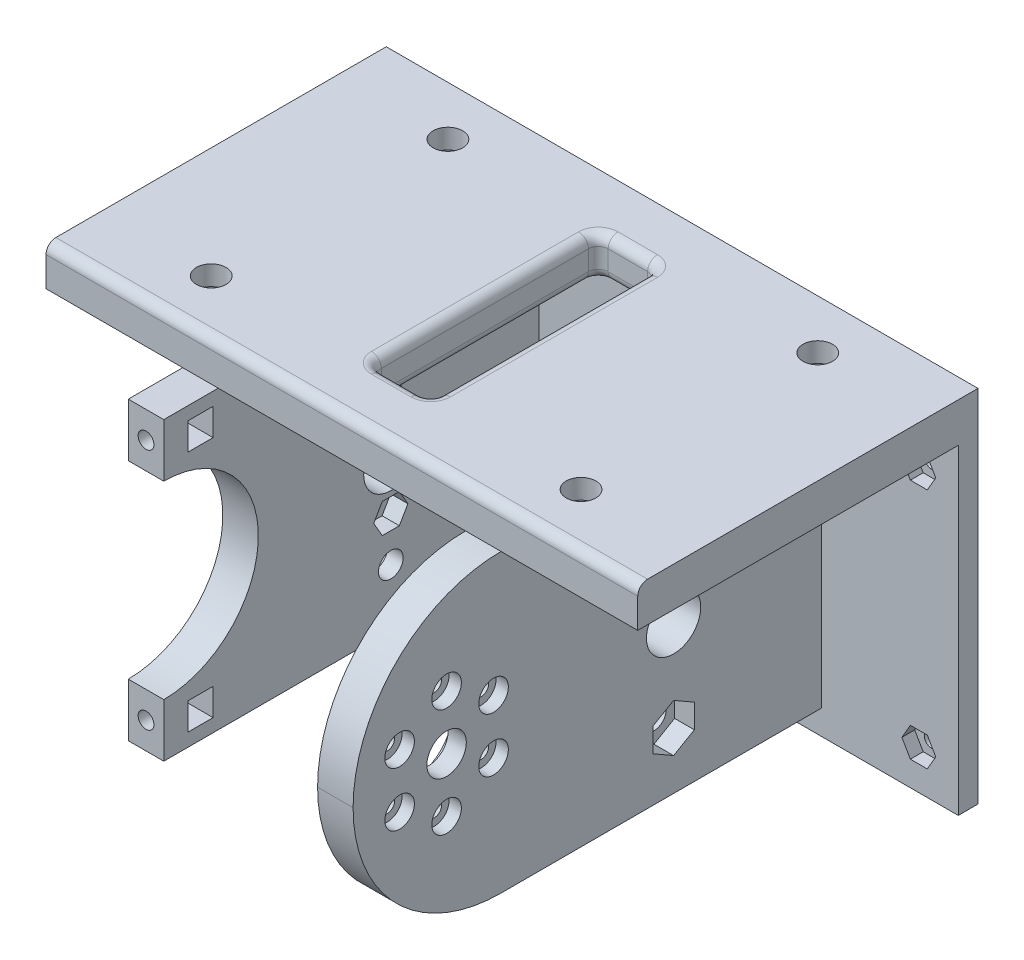
SolidWorks part; units mm, degrees
ref_plane "Front Plane" through (0, 0, 0) normal (0, 0, 1) x (1, 0, 0)
ref_plane "Top Plane" through (0, 0, 0) normal (0, 1, 0) x (1, 0, 0)
ref_plane "Right Plane" through (0, 0, 0) normal (1, 0, 0) x (0, 0, -1)
sketch "Sketch1" plane through (0, 0, 0) normal (0, 1, 0) x (1, 0, 0)
  line L0 (0, 18.2197) -> (0, -18.3609) construction
  line L1 (-19.3496, 0) -> (20.197, 0) construction
  line L2 (-37.5, 0) -> (-37.5, -10) construction
  line L3 (60, 35) -> (-60, 35)
  line L4 (-60, 35) -> (-60, -35)
  line L5 (60, -35) -> (-60, -35)
  line L6 (60, 35) -> (60, -35)
  line L7 (6, 23) -> (-6, 23)
  line L8 (-6, 23) -> (-6, -23)
  line L9 (6, -23) -> (-6, -23)
  line L10 (6, 23) -> (6, -23)
  circle A0 centre (-37.5, 0) radius 10 construction
  circle A6 centre (-37.5, 24) radius 3
  circle A7 centre (-37.5, 24) radius 3.4 construction
  circle A8 centre (-37.5, -24) radius 3
  circle A9 centre (-37.5, -24) radius 3.4 construction
  circle A10 centre (37.5, 24) radius 3
  circle A11 centre (37.5, 24) radius 3.4 construction
  circle A12 centre (37.5, 0) radius 10 construction
  circle A13 centre (37.5, -24) radius 3.4 construction
  circle A14 centre (37.5, -24) radius 3
  point P18 (-60, 0)
  point P20 (0, 35)
  point P21 (0, -35)
  point P33 (-6, 0)
  point P35 (0, -23)
  point P36 (0, 23)
  dimension "D1" = 20
  dimension "D3" = 6.8
  dimension "D4" = 48
  dimension "D5" = 75
  dimension "D2" = 6
  dimension "D6" = 120
  dimension "D7" = 70
  dimension "D8" = 12
  dimension "D9" = 46
extrude "Boss-Extrude1" add sketch "Sketch1" along normal blind 8
fillet "Fillet1" radius 2 4 edges at (6, 4, 23) (-6, 4, 23) (6, 4, -23) (-6, 4, -23)
sketch "Sketch2" plane through (0, 0, 0) normal (0, -1, 0) x (1, 0, 0)
  line L0 (-60, -35) -> (-60, -30)
  line L1 (-60, -35) -> (-60, 35) construction
  line L2 (-60, -30) -> (60, -30)
  line L3 (60, 35) -> (60, -35) construction
  line L4 (60, -30) -> (60, -35)
  line L5 (60, -35) -> (-60, -35)
  dimension "D1" = 5
extrude "Boss-Extrude2" add sketch "Sketch2" along normal blind 65
sketch "Sketch3" plane through (0, 0, -30) normal (0, 0, 1) x (1, 0, 0)
  line L0 (0, 0) -> (0, -65) construction
  line L1 (60, 0) -> (-60, 0) construction
  line L2 (60, -65) -> (-60, -65) construction
  line L3 (0, -32.5) -> (-60, -32.5) construction
  line L4 (-60, -65) -> (-60, 0) construction
  line L5 (0, -32.5) -> (60, -32.5) construction
  line L6 (60, -65) -> (60, 0) construction
  line L8 (30, 0) -> (30, -65) construction
  line L9 (-25.075, 0) -> (-32.275, 0)
  line L10 (-32.275, 0) -> (-32.275, -60)
  line L11 (-32.275, -60) -> (-25.075, -60)
  line L12 (-25.075, 0) -> (-25.075, -60)
  line L13 (25.075, 0) -> (25.075, -60)
  line L14 (32.275, -60) -> (25.075, -60)
  line L15 (32.275, 0) -> (32.275, -60)
  line L16 (25.075, 0) -> (32.275, 0)
  point P18 (30, -32.5)
  dimension "D1" = 7.2
  dimension "D2" = 50.15
  dimension "D3" = 60
extrude "Boss-Extrude3" add sketch "Sketch3" along normal blind 45
sketch "Sketch4" plane through (-32.275, 0, 0) normal (-1, 0, 0) x (0, 0, 1)
  line L0 (0, 0) -> (0, -60) construction
  line L1 (15, -60) -> (-30, -60) construction
  line L2 (-30, -30) -> (15, -30) construction
  line L3 (-30, 0) -> (-30, -60) construction
  line L4 (15, 0) -> (15, -60) construction
  circle A0 centre (0, -30) radius 5.5
  circle A1 centre (0, -30) radius 18.5 construction
  circle A2 centre (0, -11.5) radius 2.5
  circle A3 centre (0, -48.5) radius 2.5
  dimension "D1" = 11
  dimension "D2" = 37
  dimension "5" = 5
extrude "Cut-Extrude1" cut sketch "Sketch4" against normal through all both and the other way through all
sketch "Sketch5" plane through (-32.275, 0, 0) normal (-1, 0, 0) x (0, 0, 1)
  line L0 (-30, 0) -> (-30, -60) construction
  line L1 (4.2, -9.0751) -> (0, -6.6503)
  line L2 (0, -6.6503) -> (-4.2, -9.0751)
  line L3 (-4.2, -9.0751) -> (-4.2, -13.9249)
  line L4 (-4.2, -13.9249) -> (0, -16.3497)
  line L5 (0, -16.3497) -> (4.2, -13.9249)
  line L6 (4.2, -13.9249) -> (4.2, -9.0751)
  line L7 (4.2, -46.0751) -> (0, -43.6503)
  line L8 (0, -43.6503) -> (-4.2, -46.0751)
  line L9 (-4.2, -46.0751) -> (-4.2, -50.9249)
  line L10 (-4.2, -50.9249) -> (0, -53.3497)
  line L11 (0, -53.3497) -> (4.2, -50.9249)
  line L12 (4.2, -50.9249) -> (4.2, -46.0751)
  line L13 (-30, -65) -> (-30, 0) construction
  circle A0 centre (0, -11.5) radius 4.2 construction
  circle A1 centre (0, -48.5) radius 4.2 construction
  point P10 (2.1, -52.1373)
  dimension "D1" = 8.4
  dimension "D2" = 8.4
extrude "Cut-Extrude2" cut sketch "Sketch5" against normal blind 4
sketch "Sketch6" plane through (32.275, 0, 0) normal (1, 0, 0) x (0, 0, -1)
  line L0 (30, -65) -> (30, 0) construction
  line L1 (4.2, -13.9249) -> (4.2, -9.0751)
  line L2 (4.2, -9.0751) -> (0, -6.6503)
  line L3 (0, -6.6503) -> (-4.2, -9.0751)
  line L4 (-4.2, -9.0751) -> (-4.2, -13.9249)
  line L5 (-4.2, -13.9249) -> (0, -16.3497)
  line L6 (0, -16.3497) -> (4.2, -13.9249)
  line L7 (-4.2, -46.0751) -> (-4.2, -50.9249)
  line L8 (-4.2, -50.9249) -> (0, -53.3497)
  line L9 (0, -53.3497) -> (4.2, -50.9249)
  line L10 (4.2, -50.9249) -> (4.2, -46.0751)
  line L11 (4.2, -46.0751) -> (0, -43.6503)
  line L12 (0, -43.6503) -> (-4.2, -46.0751)
  circle A0 centre (0, -11.5) radius 4.2 construction
  circle A1 centre (0, -48.5) radius 4.2 construction
  dimension "D1" = 8.4
  dimension "D2" = 8.4
extrude "Cut-Extrude3" cut sketch "Sketch6" against normal blind 4
sketch "Sketch7" plane through (0, 0, 0) normal (0, -1, 0) x (1, 0, 0)
  line L0 (32.275, 15) -> (32.275, -30) construction
  line L1 (42.7, -20.9978) -> (37.5, -17.9956)
  line L2 (37.5, -17.9956) -> (32.3, -20.9978)
  line L3 (32.3, -20.9978) -> (32.3, -27.0022)
  line L4 (32.3, -27.0022) -> (37.5, -30.0044)
  line L5 (37.5, -30.0044) -> (42.7, -27.0022)
  line L6 (42.7, -27.0022) -> (42.7, -20.9978)
  line L7 (42.7, 27.0022) -> (37.5, 30.0044)
  line L8 (37.5, 30.0044) -> (32.3, 27.0022)
  line L9 (32.3, 27.0022) -> (32.3, 20.9978)
  line L10 (32.3, 20.9978) -> (37.5, 17.9956)
  line L11 (37.5, 17.9956) -> (42.7, 20.9978)
  line L12 (42.7, 20.9978) -> (42.7, 27.0022)
  line L13 (0, 0) -> (0, 40) construction
  line L14 (-42.7, -27.0022) -> (-42.7, -20.9978)
  line L15 (-37.5, -30.0044) -> (-42.7, -27.0022)
  line L16 (-32.3, -27.0022) -> (-37.5, -30.0044)
  line L17 (-32.3, -20.9978) -> (-32.3, -27.0022)
  line L18 (-37.5, -17.9956) -> (-32.3, -20.9978)
  line L19 (-42.7, -20.9978) -> (-37.5, -17.9956)
  line L20 (-42.7, 20.9978) -> (-42.7, 27.0022)
  line L21 (-37.5, 17.9956) -> (-42.7, 20.9978)
  line L22 (-32.3, 20.9978) -> (-37.5, 17.9956)
  line L23 (-32.3, 27.0022) -> (-32.3, 20.9978)
  line L24 (-37.5, 30.0044) -> (-32.3, 27.0022)
  line L25 (-42.7, 27.0022) -> (-37.5, 30.0044)
  circle A0 centre (37.5, -24) radius 5.2 construction
  circle A1 centre (37.5, 24) radius 5.2 construction
  circle A3 centre (-37.5, -24) radius 5.2 construction
  circle A4 centre (-37.5, 24) radius 5.2 construction
  dimension "D1" = 10.4
  dimension "D2" = 10.4
extrude "Cut-Extrude4" cut sketch "Sketch7" against normal blind 4
fillet "Fillet3" radius 2 17 edges at (5.4142, 0, 22.4142) (0, 0, 23) (-5.4142, 0, 22.4142) (-6, 0, 0) (-5.4142, 0, -22.4142) (0, 0, -23) (5.4142, 0, -22.4142) (5.4142, 8, 22.4142) (0, 8, 23) (-5.4142, 8, 22.4142) (-6, 8, 0) (-5.4142, 8, -22.4142) (0, 8, -23) (5.4142, 8, -22.4142) (6, 0, 0) (6, 8, 0) (0, 8, 35)
sketch "Sketch10" plane through (0, 0, 15) normal (0, 0, 1) x (1, 0, 0)
  line L8 (-25.075, -60) -> (-25.075, 0)
  line L9 (-25.075, 0) -> (-32.275, 0)
  line L10 (-32.275, 0) -> (-32.275, -60)
  line L11 (-32.275, -60) -> (-25.075, -60)
  line L12 (-25.075, -60) -> (-25.075, 0)
  line L13 (-25.075, 0) -> (-32.275, 0)
  line L14 (-32.275, 0) -> (-32.275, -60)
  line L15 (-32.275, -60) -> (-25.075, -60)
  line L16 (32.275, 0) -> (25.075, 0)
  line L17 (25.075, 0) -> (25.075, -60)
  line L18 (25.075, -60) -> (32.275, -60)
  line L19 (32.275, -60) -> (32.275, 0)
  line L20 (32.275, 0) -> (25.075, 0)
  line L21 (25.075, 0) -> (25.075, -60)
  line L22 (25.075, -60) -> (32.275, -60)
  line L23 (32.275, -60) -> (32.275, 0)
  dimension "D1" = 0
  dimension "D2" = 0
extrude "Boss-Extrude4" add sketch "Sketch10" along normal blind 50
sketch "Sketch11" plane through (32.275, 0, 0) normal (1, 0, 0) x (0, 0, -1)
  line L0 (0, -30) -> (-46.04, -30) construction
  circle A0 centre (-46.04, -30) radius 4
  dimension "D2" = 8
  dimension "D1" = 46.04
extrude "Cut-Extrude7" cut sketch "Sketch11" against normal through all
sketch "Sketch13" plane through (32.275, 0, 0) normal (1, 0, 0) x (0, 0, -1)
  circle A0 centre (-46.04, -30) radius 11 construction
  circle A1 centre (-46.04, -19) radius 1.5
  circle A2 centre (-55.5663, -24.5) radius 1.5
  circle A3 centre (-55.5663, -35.5) radius 1.5
  circle A4 centre (-46.04, -41) radius 1.5
  circle A5 centre (-36.5137, -35.5) radius 1.5
  circle A6 centre (-36.5137, -24.5) radius 1.5
  point P17 (-46.04, -30)
  dimension "D1" = 22
  dimension "D2" = 3
  dimension "D3" = 6
extrude "Cut-Extrude8" cut sketch "Sketch13" against normal up to surface (7.2 mm away) up to face at (25.075, -30, 42.04)
sketch "Sketch15" plane through (32.275, 0, 0) normal (1, 0, 0) x (0, 0, -1)
  line L0 (-47.9433, -23.3677) -> (-5.4066, -11.1604) construction
  line L1 (0, -30) -> (-46.04, -30) construction
  line L2 (-47.9433, -36.6323) -> (-5.4066, -48.8396) construction
  line L3 (-24.2688, -6.1699) -> (-15.9934, -35.0059) construction
  line L4 (-21.8658, -5.4803) -> (-26.6718, -6.8595)
  line L5 (-26.6718, -6.8595) -> (-18.3964, -35.6956)
  line L6 (-18.3964, -35.6956) -> (-13.5904, -34.3163)
  line L7 (-21.8658, -5.4803) -> (-13.5904, -34.3163)
  circle A0 centre (0, -30) radius 19.6 construction
  circle A1 centre (-46.04, -30) radius 6.9 construction
  circle A2 centre (-46.04, -30) radius 19 construction
  circle A3 centre (0, -30) radius 22 construction
  circle A4 centre (-46.04, -30) radius 8 construction
  circle A5 centre (-24.0903, -6.7918) radius 6.35 construction
  dimension "D1" = 39.2
  dimension "D2" = 13.8
  dimension "D3" = 38
  dimension "D4" = 44
  dimension "D5" = 16
  dimension "D10" = 12.7
  dimension "D6" = 10
  dimension "D7" = 20
  dimension "D8" = 27.5
  dimension "D9" = 5
extrude "Cut-Extrude9" [suppressed] cut sketch "Sketch15" against normal up to surface (7.2 mm away)
sketch "Sketch16" plane through (-32.275, 0, 0) normal (-1, 0, 0) x (0, 0, 1)
  circle A0 centre (0, -30) radius 9.525 construction
  circle A1 centre (0, -20.475) radius 1.5
  circle A2 centre (0, -39.525) radius 1.5
  dimension "D1" = 19.05
  dimension "D2" = 3
extrude "Cut-Extrude10" cut sketch "Sketch16" against normal up to surface (7.2 mm away) up to face at (-25.075, -30, 50.04)
sketch "Sketch18" plane through (-25.075, 0, 0) normal (1, 0, 0) x (0, 0, -1)
  line L1 (3.4641, -20.475) -> (1.7321, -17.475)
  line L2 (1.7321, -17.475) -> (-1.7321, -17.475)
  line L3 (-1.7321, -17.475) -> (-3.4641, -20.475)
  line L4 (-3.4641, -20.475) -> (-1.7321, -23.475)
  line L5 (-1.7321, -23.475) -> (1.7321, -23.475)
  line L6 (1.7321, -23.475) -> (3.4641, -20.475)
  line L7 (3.4641, -39.525) -> (1.7321, -36.525)
  line L8 (1.7321, -36.525) -> (-1.7321, -36.525)
  line L9 (-1.7321, -36.525) -> (-3.4641, -39.525)
  line L10 (-3.4641, -39.525) -> (-1.7321, -42.525)
  line L11 (-1.7321, -42.525) -> (1.7321, -42.525)
  line L12 (1.7321, -42.525) -> (3.4641, -39.525)
  circle A0 centre (0, -20.475) radius 3 construction
  circle A1 centre (0, -39.525) radius 3 construction
  dimension "D1" = 6
  dimension "D2" = 6
extrude "Cut-Extrude11" cut sketch "Sketch18" against normal blind 3.5
sketch "Sketch20" plane through (-32.275, 0, 0) normal (-1, 0, 0) x (0, 0, 1)
  circle A0 centre (46.04, -30) radius 19.175
  dimension "D1" = 38.35
extrude "Cut-Extrude12" cut sketch "Sketch20" against normal up to surface (7.2 mm away) up to face at (-25.075, -20.475, 0)
sketch "Sketch21" plane through (25.075, 0, 0) normal (-1, 0, 0) x (0, 0, 1)
  circle A0 centre (46.04, -30) radius 8.5
  dimension "D1" = 17
extrude "Cut-Extrude13" cut sketch "Sketch21" against normal blind 3.5
sketch "Sketch22" plane through (-32.275, 0, 0) normal (-1, 0, 0) x (0, 0, 1)
  line L1 (46.04, -30) -> (46.04, 0)
  line L2 (65, 0) -> (35, 0) construction
  line L10 (46.04, -30) -> (46.04, -60)
  line L11 (65, -60) -> (-30, -60) construction
  line L12 (46.04, 0) -> (65, 0)
  line L13 (46.04, -60) -> (65, -60)
  line L14 (65, -60) -> (65, 0)
extrude "Cut-Extrude14" cut sketch "Sketch22" against normal up to surface (7.2 mm away) up to face at (-25.075, -20.475, 0)
fillet "Fillet4" radius 30 2 edges at (28.675, 0, 65) (28.675, -60, 65)
sketch "Sketch25" plane through (32.275, 0, 0) normal (1, 0, 0) x (0, 0, -1)
  circle A0 centre (-55.5663, -24.5) radius 3
  circle A1 centre (-46.04, -19) radius 3
  circle A2 centre (-36.5137, -24.5) radius 3
  circle A3 centre (-36.5137, -35.5) radius 3
  circle A4 centre (-46.04, -41) radius 3
  circle A5 centre (-55.5663, -35.5) radius 3
  dimension "D1" = 6
extrude "Cut-Extrude16" cut sketch "Sketch25" against normal blind 2.5
sketch "Sketch26" plane through (-32.275, 0, 0) normal (-1, 0, 0) x (0, 0, 1)
  line L0 (46.04, -5.4125) -> (34.0392, -5.4125) construction
  line L2 (46.04, -54.5875) -> (31.5951, -54.5875) construction
  line L4 (46.04, -49.175) -> (46.04, -60) construction
  line L5 (36.04, -2.6625) -> (41.14, -2.6625)
  line L6 (36.04, -2.6625) -> (36.04, -8.1625)
  line L7 (36.04, -8.1625) -> (41.14, -8.1625)
  line L8 (41.14, -2.6625) -> (41.14, -8.1625)
  line L9 (36.04, -2.6625) -> (41.14, -8.1625) construction
  line L10 (36.04, -8.1625) -> (41.14, -2.6625) construction
  line L11 (36.04, -51.8375) -> (41.14, -51.8375)
  line L12 (36.04, -51.8375) -> (36.04, -57.3375)
  line L13 (36.04, -57.3375) -> (41.14, -57.3375)
  line L14 (41.14, -51.8375) -> (41.14, -57.3375)
  line L15 (36.04, -51.8375) -> (41.14, -57.3375) construction
  line L16 (36.04, -57.3375) -> (41.14, -51.8375) construction
  line L17 (46.04, 0) -> (46.04, -10.825) construction
  point P8 (38.59, -5.4125)
  point P13 (38.59, -54.5875)
  dimension "D1" = 5.1
  dimension "D2" = 5.5
  dimension "D3" = 5.5
  dimension "D4" = 5.1
  dimension "D5" = 10
  dimension "D6" = 10
extrude "Cut-Extrude17" cut sketch "Sketch26" against normal up to surface (7.2 mm away) up to face at (-25.075, -20.475, 0)
sketch "Sketch28" plane through (0, 0, 46.04) normal (0, 0, 1) x (1, 0, 0)
  line L0 (-28.675, 0) -> (-28.675, -10.825) construction
  line L1 (-25.075, 0) -> (-32.275, 0) construction
  line L2 (-25.075, -10.825) -> (-32.275, -10.825) construction
  line L3 (-32.275, -5.4125) -> (-25.075, -5.4125) construction
  line L4 (-32.275, 0) -> (-32.275, -10.825) construction
  line L5 (-25.075, -10.825) -> (-25.075, 0) construction
  line L6 (-28.675, -49.175) -> (-28.675, -60) construction
  line L7 (-32.275, -49.175) -> (-25.075, -49.175) construction
  line L8 (-25.075, -60) -> (-32.275, -60) construction
  line L9 (-32.275, -54.5875) -> (-25.075, -54.5875) construction
  line L10 (-32.275, -49.175) -> (-32.275, -60) construction
  line L11 (-25.075, -60) -> (-25.075, -49.175) construction
  circle A0 centre (-28.675, -5.4125) radius 1.6
  circle A1 centre (-28.675, -54.5875) radius 1.6
  dimension "D1" = 3.2
  dimension "D2" = 3.2
extrude "Cut-Extrude18" cut sketch "Sketch28" against normal blind 10
sketch "Sketch29" plane through (0, 0, -30) normal (0, 0, 1) x (1, 0, 0)
  line L0 (-60, -65) -> (-60, 0) construction
  line L1 (-60, 0) -> (-32.275, 0) construction
  line L2 (60, -65) -> (-60, -65) construction
  line L3 (60, -65) -> (60, 0) construction
  line L4 (32.275, 0) -> (60, 0) construction
  circle A0 centre (-52, -8) radius 1.5
  circle A1 centre (-52, -57) radius 1.5
  circle A2 centre (52, -57) radius 1.5
  circle A3 centre (52, -8) radius 1.5
  dimension "D1" = 3
  dimension "D2" = 8
  dimension "D3" = 8
  dimension "D4" = 8
  dimension "D5" = 8
  dimension "D6" = 8
  dimension "D7" = 8
  dimension "D8" = 8
  dimension "D9" = 8
extrude "Cut-Extrude19" cut sketch "Sketch29" against normal blind 10
sketch "Sketch30" plane through (0, 0, -30) normal (0, 0, 1) x (1, 0, 0)
  line L1 (-48.5648, -8) -> (-50.2824, -5.025)
  line L2 (-50.2824, -5.025) -> (-53.7176, -5.025)
  line L3 (-53.7176, -5.025) -> (-55.4352, -8)
  line L4 (-55.4352, -8) -> (-53.7176, -10.975)
  line L5 (-53.7176, -10.975) -> (-50.2824, -10.975)
  line L6 (-50.2824, -10.975) -> (-48.5648, -8)
  line L7 (-48.5648, -57) -> (-50.2824, -54.025)
  line L8 (-50.2824, -54.025) -> (-53.7176, -54.025)
  line L9 (-53.7176, -54.025) -> (-55.4352, -57)
  line L10 (-55.4352, -57) -> (-53.7176, -59.975)
  line L11 (-53.7176, -59.975) -> (-50.2824, -59.975)
  line L12 (-50.2824, -59.975) -> (-48.5648, -57)
  line L13 (55.4352, -57) -> (53.7176, -54.025)
  line L14 (53.7176, -54.025) -> (50.2824, -54.025)
  line L15 (50.2824, -54.025) -> (48.5648, -57)
  line L16 (48.5648, -57) -> (50.2824, -59.975)
  line L17 (50.2824, -59.975) -> (53.7176, -59.975)
  line L18 (53.7176, -59.975) -> (55.4352, -57)
  line L19 (55.4352, -8) -> (53.7176, -5.025)
  line L20 (53.7176, -5.025) -> (50.2824, -5.025)
  line L21 (50.2824, -5.025) -> (48.5648, -8)
  line L22 (48.5648, -8) -> (50.2824, -10.975)
  line L23 (50.2824, -10.975) -> (53.7176, -10.975)
  line L24 (53.7176, -10.975) -> (55.4352, -8)
  circle A0 centre (-52, -8) radius 2.975 construction
  circle A1 centre (-52, -57) radius 2.975 construction
  circle A2 centre (52, -57) radius 2.975 construction
  circle A3 centre (52, -8) radius 2.975 construction
  point P28 (-52, -10.975)
  dimension "D1" = 5.95
  dimension "D2" = 5.95
  dimension "D3" = 5.95
  dimension "D4" = 5.95
extrude "Cut-Extrude20" cut sketch "Sketch30" against normal blind 2.6
chamfer "Chamfer1" distance 1 angle 45 4 edges at (60, -28.5, -35) (0, -65, -35) (0, 8, -35) (-60, -28.5, -35)
